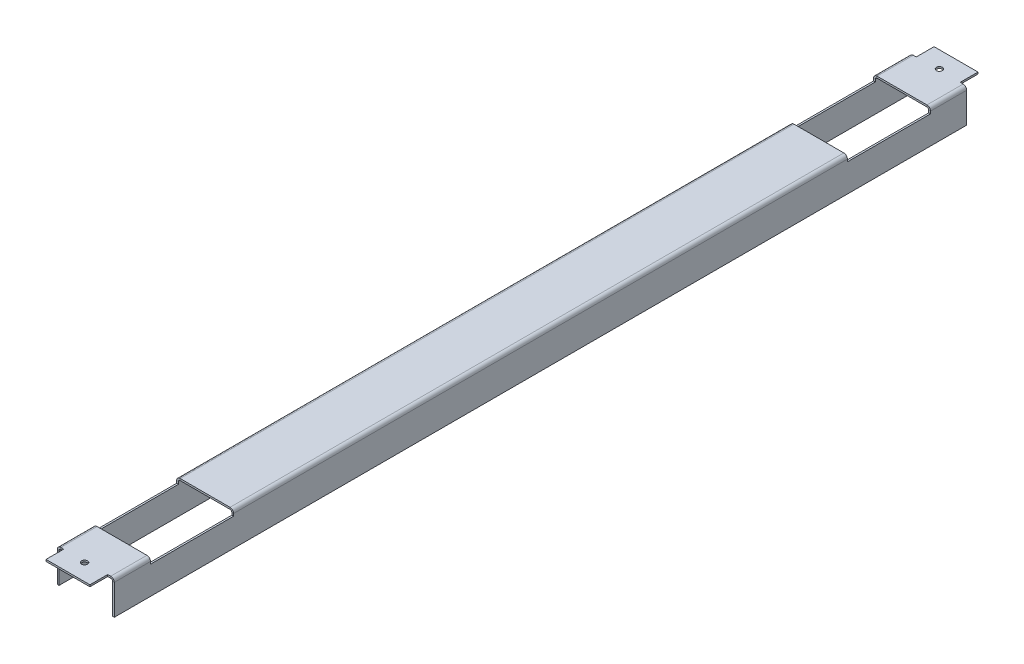
SolidWorks part; units mm, degrees
note: The reader was unsure of these and kept them because the rebuilt part matched: thickness of "Базовая кромка1", "Листовой металл3", "Листовой металл4", "Листовой металл5"; bend radius of "Базовая кромка1", "Основание1", "Основание2".
material "Оцинкованная сталь"
ref_plane "Спереди" through (0, 0, 0) normal (0, 0, 1) x (1, 0, 0)
ref_plane "Сверху" through (0, 0, 0) normal (0, 1, 0) x (1, 0, 0)
ref_plane "Справа" through (0, 0, 0) normal (1, 0, 0) x (0, 0, -1)
sketch "Эскиз1" plane through (0, 0, 0) normal (0, 0, 1) x (1, 0, 0)
  line L0 (-22.5, 0) -> (22.5, 0)
  line L1 (22.5, 0) -> (22.5, -27)
  line L2 (-22.5, 0) -> (-22.5, -27)
  point P3 (0, 0)
  dimension "D1" = 27
  dimension "D2" = 45
base flange "Базовая кромка1" sketch "Эскиз1" end condition mid plane depth 748 reverse direction no thickness 1.5 reverse thickness direction no bend radius 1.5
bend "Основание1" bend radius 1.5 bend angle 90 parameters "D5"=1
bend "Основание2" bend radius 1.5 bend angle 90 parameters "D5"=2
sketch "Эскиз6" plane through (0, 1.5, 0) normal (0, 1, 0) x (1, 0, 0)
  line L0 (21, -374) -> (-21, -374) construction
  line L1 (-18.5, -374) -> (-25, -374)
  line L2 (-18.5, -374) -> (-18.5, -359)
  line L3 (-18.5, -359) -> (-25, -359)
  line L4 (-25, -374) -> (-25, -359)
  line L5 (-21, -374) -> (-21, 374) construction
  line L6 (18.5, -374) -> (25, -374)
  line L7 (18.5, -374) -> (18.5, -359)
  line L8 (18.5, -359) -> (25, -359)
  line L9 (25, -374) -> (25, -359)
  line L10 (21, -374) -> (21, 374) construction
  line L11 (-50, 0) -> (50, 0) construction
  line L12 (25, 374) -> (25, 359)
  line L13 (18.5, 359) -> (25, 359)
  line L14 (18.5, 374) -> (18.5, 359)
  line L15 (18.5, 374) -> (25, 374)
  line L16 (-25, 374) -> (-25, 359)
  line L17 (-18.5, 359) -> (-25, 359)
  line L18 (-18.5, 374) -> (-18.5, 359)
  line L19 (-18.5, 374) -> (-25, 374)
  circle A0 centre (0, -360) radius 2.5
  circle A1 centre (0, 360) radius 2.5
  point P10 (0, -374)
  dimension "D6" = 5
  dimension "D7" = 14
  dimension "D1" = 37
  dimension "D2" = 15
  dimension "D3" = 18.5
  dimension "D4" = 4
  dimension "D5" = 4
extrude "Вырез-Вытянуть1" cut sketch "Эскиз6" against normal through all normal cut yes
sketch "Эскиз7" plane through (0, 1.5, 0) normal (0, 1, 0) x (1, 0, 0)
  line L0 (18.5, -374) -> (-18.5, -374) construction
  line L1 (-25, -328.5) -> (25, -328.5)
  line L2 (-25, -328.5) -> (-25, -258.5)
  line L3 (-25, -258.5) -> (25, -258.5)
  line L4 (25, -328.5) -> (25, -258.5)
  line L5 (-21, -359) -> (-21, 359) construction
  line L6 (21, -359) -> (21, 359) construction
  line L7 (-50, 0) -> (50, 0) construction
  line L8 (25, 328.5) -> (25, 258.5)
  line L9 (-25, 258.5) -> (25, 258.5)
  line L10 (-25, 328.5) -> (-25, 258.5)
  line L11 (-25, 328.5) -> (25, 328.5)
  dimension "D1" = 45.5
  dimension "D2" = 70
  dimension "D3" = 4
  dimension "D4" = 4
extrude "Вырез-Вытянуть2" cut sketch "Эскиз7" against normal blind 5 normal cut yes
sketch "Сгиб-Линии1" [suppressed] plane through (0, 0, 0) normal (0, 1, 0) x (1, 0, 0)
sketch "Граничная рамка1" [suppressed] plane through (0, 0, 0) normal (0, 1, 0) x (1, 0, 0)
sheet metal parameters "Листовой металл3" thickness 1.5 parameters "D1"=1.5
flat pattern "Развертка3" [suppressed]
sketch "Сгиб-Линии2" plane through (0, 0, 0) normal (0, 1, 0) x (1, 0, 0)
sketch "Граничная рамка2" [suppressed] plane through (0, 0, 0) normal (0, 1, 0) x (1, 0, 0)
bend of the flat pattern "Плоское состояние-<Основание1>1"
bend of the flat pattern "Плоское состояние-<Основание2>1"
sheet metal parameters "Листовой металл4" thickness 1.5 parameters "D1"=1.5, "D7"=1
flat pattern "Развертка3" [suppressed]
sketch "Сгиб-Линии2" plane through (0, 0, 0) normal (0, 1, 0) x (1, 0, 0)
sketch "Граничная рамка2" [suppressed] plane through (0, 0, 0) normal (0, 1, 0) x (1, 0, 0)
bend of the flat pattern "Плоское состояние-<Основание1>1"
bend of the flat pattern "Плоское состояние-<Основание2>1"
sheet metal parameters "Листовой металл5" thickness 1.5 parameters "D1"=1.5, "D7"=1
flat pattern "Развертка3"
sketch "Сгиб-Линии2" plane through (0, 0, 0) normal (0, -1, 0) x (-1, 0, 0)
  line L0 (-22.7671, -384) -> (-22.7671, 384) construction
  line L1 (22.7671, 384) -> (22.7671, -384) construction
  line L2 (-22.7671, -384) -> (-22.7671, -353.5) construction
  line L3 (-22.7671, 353.5) -> (-22.7671, 384) construction
  line L4 (-22.7671, -283.5) -> (-22.7671, 283.5) construction
  line L5 (22.7671, -353.5) -> (22.7671, -384) construction
  line L6 (22.7671, 384) -> (22.7671, 353.5) construction
  line L7 (22.7671, 283.5) -> (22.7671, -283.5) construction
sketch3d "Граничная рамка2" [suppressed]
  line L0 (-72.5343, 0, 0) -> (-72.5343, 798, 0) construction
  line L1 (27.5343, 0, 0) -> (27.5343, 798, 0) construction
  line L2 (-72.5343, 0, 0) -> (27.5343, 0, 0) construction
  line L3 (-72.5343, 798, 0) -> (27.5343, 798, 0) construction
bend of the flat pattern "Плоское состояние-<Основание1>1"
bend of the flat pattern "Плоское состояние-<Основание2>1"
